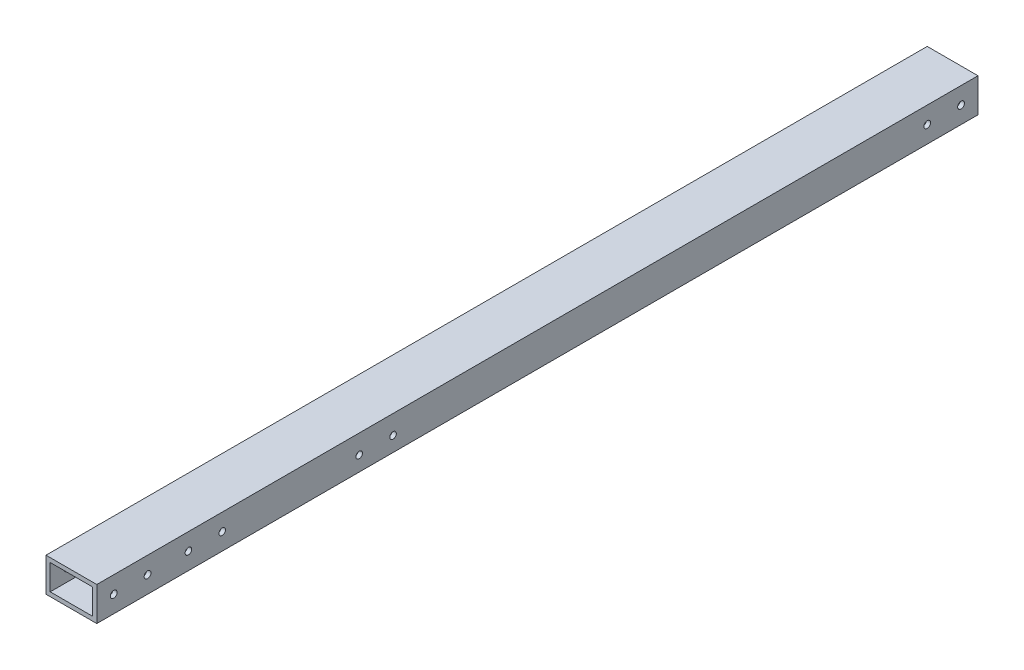
SolidWorks part; units mm, degrees
ref_plane "Front Plane" through (0, 0, 0) normal (0, 0, 1) x (1, 0, 0)
ref_plane "Top Plane" through (0, 0, 0) normal (0, 1, 0) x (1, 0, 0)
ref_plane "Right Plane" through (0, 0, 0) normal (1, 0, 0) x (0, 0, -1)
sketch "Sketch1" plane through (0, 0, 0) normal (0, 0, 1) x (1, 0, 0)
  line L0 (-15.875, 9.525) -> (15.875, 9.525)
  line L2 (-19.05, 12.7) -> (19.05, 12.7)
  line L3 (-19.05, 12.7) -> (-19.05, -12.7)
  line L4 (-19.05, -12.7) -> (19.05, -12.7)
  line L5 (19.05, 12.7) -> (19.05, -12.7)
  line L10 (15.875, 9.525) -> (15.875, -9.525)
  line L11 (-15.875, -9.525) -> (15.875, -9.525)
  line L12 (-15.875, 9.525) -> (-15.875, -9.525)
  point P12 (0, 12.7)
  point P14 (19.05, 0)
  dimension "Wall Thickness" = 3.175
  dimension "Outside Width" = 38.1
  dimension "Outside Height" = 25.4
  dimension "Inside Height" = 19.05
  dimension "Inside Width" = 31.75
sketch "Sketch2" plane through (0, 0, 0) normal (1, 0, 0) x (0, 0, -1)
  line L0 (330.5556, 0) -> (-330.5556, 0)
  point P4 (0, 0)
  point P7 (-330.5556, 0)
  point P10 (330.5556, 0)
  dimension "Length" = 661.1112
sketch "Sketch3" plane through (0, 0, 0) normal (0, 0, 1) x (1, 0, 0)
  line L21 (19.05, 12.7) -> (-19.05, 12.7)
  line L22 (19.05, -12.7) -> (19.05, 12.7)
  line L23 (-19.05, -12.7) -> (19.05, -12.7)
  line L24 (-19.05, 12.7) -> (-19.05, -12.7)
  line L25 (19.05, 12.7) -> (-19.05, 12.7)
  line L26 (19.05, -12.7) -> (19.05, 12.7)
  line L27 (-19.05, -12.7) -> (19.05, -12.7)
  line L28 (-19.05, 12.7) -> (-19.05, -12.7)
  line L29 (15.875, 9.525) -> (-15.875, 9.525)
  line L30 (15.875, -9.525) -> (15.875, 9.525)
  line L31 (-15.875, -9.525) -> (15.875, -9.525)
  line L32 (-15.875, 9.525) -> (-15.875, -9.525)
  line L33 (15.875, 9.525) -> (-15.875, 9.525)
  line L34 (15.875, -9.525) -> (15.875, 9.525)
  line L35 (-15.875, -9.525) -> (15.875, -9.525)
  line L36 (-15.875, 9.525) -> (-15.875, -9.525)
  dimension "D1" = 0
  dimension "D2" = 0
extrude "Boss-Extrude1" add sketch "Sketch3" along normal up to vertex (330.5556 mm away) and the other way up to vertex (330.5556 mm away) up to point (0, 0, 330.5556) other way up to point (0, 0, -330.5556)
sketch "Drawing Reference" plane through (0, 0, 0) normal (1, 0, 0) x (0, 0, -1)
  line L0 (-330.5556, 0) -> (330.5556, 0) construction
  line L1 (0, -12.7) -> (0, 12.7) construction
  line L2 (-330.5556, -12.7) -> (330.5556, -12.7) construction
  line L5 (-330.5556, 12.7) -> (330.5556, 12.7) construction
  point P7 (-303.1236, 0)
  point P8 (303.1236, 0)
  dimension "D1" = 27.432
sketch "Sketch4" plane through (-19.05, 0, 0) normal (-1, 0, 0) x (0, 0, 1)
  line L0 (-330.5556, 0) -> (-317.8556, 0)
  line L1 (-330.5556, 12.7) -> (-330.5556, -12.7) construction
  line L2 (-317.8556, 0) -> (-292.4556, 0)
  line L3 (330.5556, 12.7) -> (330.5556, -12.7) construction
  line L4 (330.5556, 0) -> (317.8556, 0)
  line L5 (317.8556, 0) -> (292.4556, 0)
  point P11 (-317.8556, 0)
  point P13 (-292.4556, 0)
  point P14 (317.8556, 0)
  point P15 (292.4556, 0)
hole_wizard "#10 Clearance Hole2" positions "Sketch11" profile "Sketch12" hole size "#10" standard "ANSI Inch" end condition through all
sketch "Sketch11" plane through (-19.05, 0, 0) normal (-1, 0, 0) x (0, 0, 1)
  point P0 (-317.8556, 0)
  point P3 (-292.4556, 0)
  point P6 (292.4556, 0)
  point P9 (317.8556, 0)
sketch "Sketch12" plane through (-19.05, 0, -317.8556) normal (0, 1, 0) x (0, 0, 1)
  line L0 (0, 0) -> (0, 38.1)
  line L1 (0, 38.1) -> (2.5527, 38.1)
  line L2 (2.5527, 38.1) -> (2.5527, 0)
  line L5 (2.5527, 0) -> (0, 0)
  line L11 (0, -6.35) -> (0, 107.95) construction
  dimension "Thru Hole Dia." = 5.1054
  dimension "Thru Hole Depth" = 38.1
hole_wizard "#10 (0.1935) Diameter Hole1" positions "Sketch14" profile "Sketch16" hole size "#10" standard "ANSI Inch" end condition through all
sketch "Sketch14" plane through (19.05, 0, 0) normal (1, 0, 0) x (0, 0, -1)
  point P10 (-133.6967, -1.5875)
  point P13 (-108.2967, -1.5875)
  point P17 (-261.8407, 0)
  point P20 (-236.4407, 0)
sketch "Sketch16" plane through (19.05, -1.5875, 133.6967) normal (0, 1, 0) x (0, 0, -1)
  line L0 (0, 0) -> (0, 38.1)
  line L1 (0, 38.1) -> (2.4574, 38.1)
  line L2 (2.4574, 38.1) -> (2.4574, 0)
  line L5 (2.4574, 0) -> (0, 0)
  line L11 (0, -6.35) -> (0, 107.95) construction
  dimension "Thru Hole Dia." = 4.9149
  dimension "Thru Hole Depth" = 38.1
sketch "Sketch17" plane through (19.05, 0, 0) normal (1, 0, 0) x (0, 0, -1)
  point P0 (-261.8407, 0)
  point P1 (-236.4407, 0)
hole_wizard "#10 (0.1935) Diameter Hole2" positions "Sketch18" profile "Sketch19" hole size "#10" standard "ANSI Inch" end condition through all
sketch "Sketch18" plane through (19.05, 0, 0) normal (1, 0, 0) x (0, 0, -1)
  point P0 (-261.8407, 0)
  point P3 (-236.4407, 0)
sketch "Sketch19" plane through (19.05, 0, 261.8407) normal (0, 1, 0) x (0, 0, -1)
  line L0 (0, 0) -> (0, 38.1)
  line L1 (0, 38.1) -> (2.4574, 38.1)
  line L2 (2.4574, 38.1) -> (2.4574, 0)
  line L5 (2.4574, 0) -> (0, 0)
  line L11 (0, -6.35) -> (0, 107.95) construction
  dimension "Thru Hole Dia." = 4.9149
  dimension "Thru Hole Depth" = 38.1
equation "\"D1@Drawing Reference\"=\"Outside Width@Sketch1\" * 0.72"
